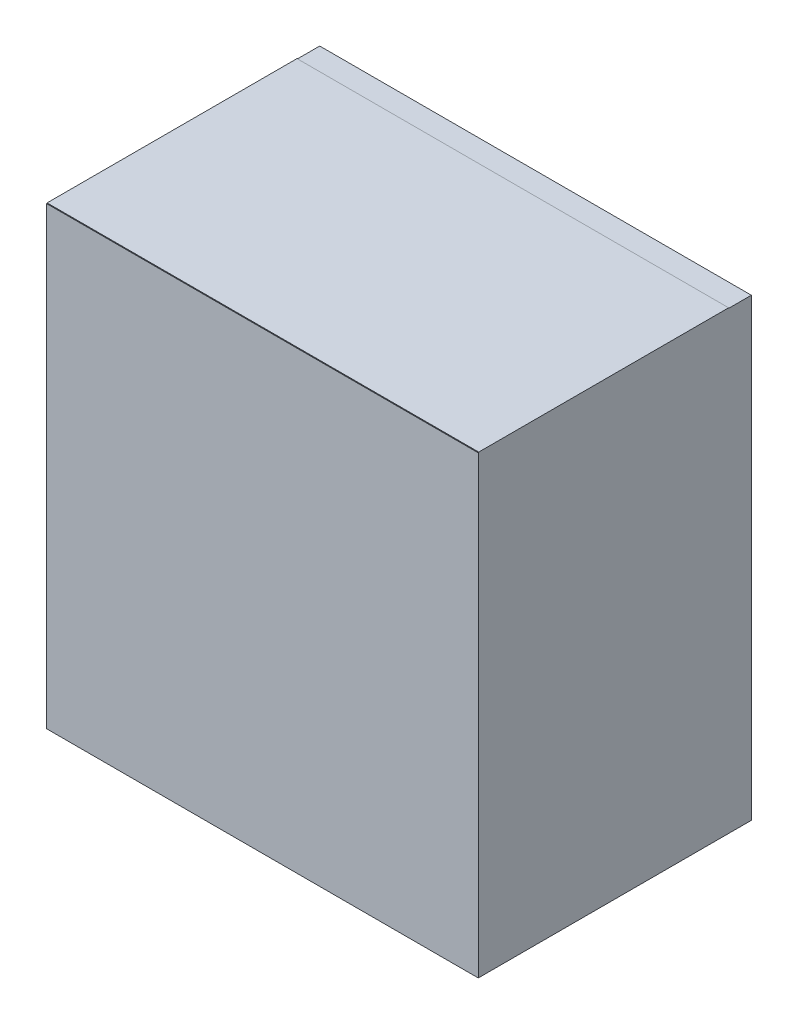
SolidWorks part; units mm, degrees
ref_plane "前视基准面" through (0, 0, 0) normal (0, 0, 1) x (1, 0, 0)
ref_plane "上视基准面" through (0, 0, 0) normal (0, 1, 0) x (1, 0, 0)
ref_plane "右视基准面" through (0, 0, 0) normal (1, 0, 0) x (0, 0, -1)
other "Configuration Table"
sketch "草图1" plane through (0, 0, 0) normal (0, 1, 0) x (1, 0, 0)
  line L1 (0, 0) -> (-950, 0)
  line L2 (0, 0) -> (0, 550)
  line L3 (0, 550) -> (-950, 550)
  line L4 (-950, 0) -> (-950, 550)
  dimension "D1" = 950
  dimension "D2" = 550
extrude "凸台-拉伸1" add sketch "草图1" along normal blind 1
ref_plane "基准面1" through (0, 1001, 0) normal (0, 1, 0) x (1, 0, 0)
sketch "草图2" plane through (0, 1001, 0) normal (0, 1, 0) x (1, 0, 0)
  line L0 (-950, 0) -> (0, 0) construction
  line L1 (0, 0) -> (0, 550) construction
  line L2 (0, 550) -> (-950, 550) construction
  line L3 (-950, 550) -> (-950, 0) construction
  line L4 (-950, 0) -> (0, 0)
  line L5 (0, 0) -> (0, 550)
  line L6 (0, 550) -> (-950, 550)
  line L7 (-950, 550) -> (-950, 0)
extrude "凸台-拉伸2" add sketch "草图2" along normal blind 1 separate body
sketch "草图3" plane through (0, 0, 0) normal (0, 0, 1) x (1, 0, 0)
  line L0 (-950, 0) -> (0, 0) construction
  line L1 (-950, 1001) -> (0, 1001) construction
  line L2 (-950, 0) -> (0, 0)
  line L3 (-950, 1001) -> (0, 1001)
  line L4 (-950, 1001) -> (-950, 0)
  line L5 (0, 1001) -> (0, 0)
extrude "凸台-拉伸3" add sketch "草图3" along normal blind 1
extrude "凸台-拉伸4" add sketch "草图3<2>" against normal blind 600
sketch "草图3<2>" plane through (0, 0, 0) normal (0, 0, 1) x (1, 0, 0) same geometry as "草图3"
